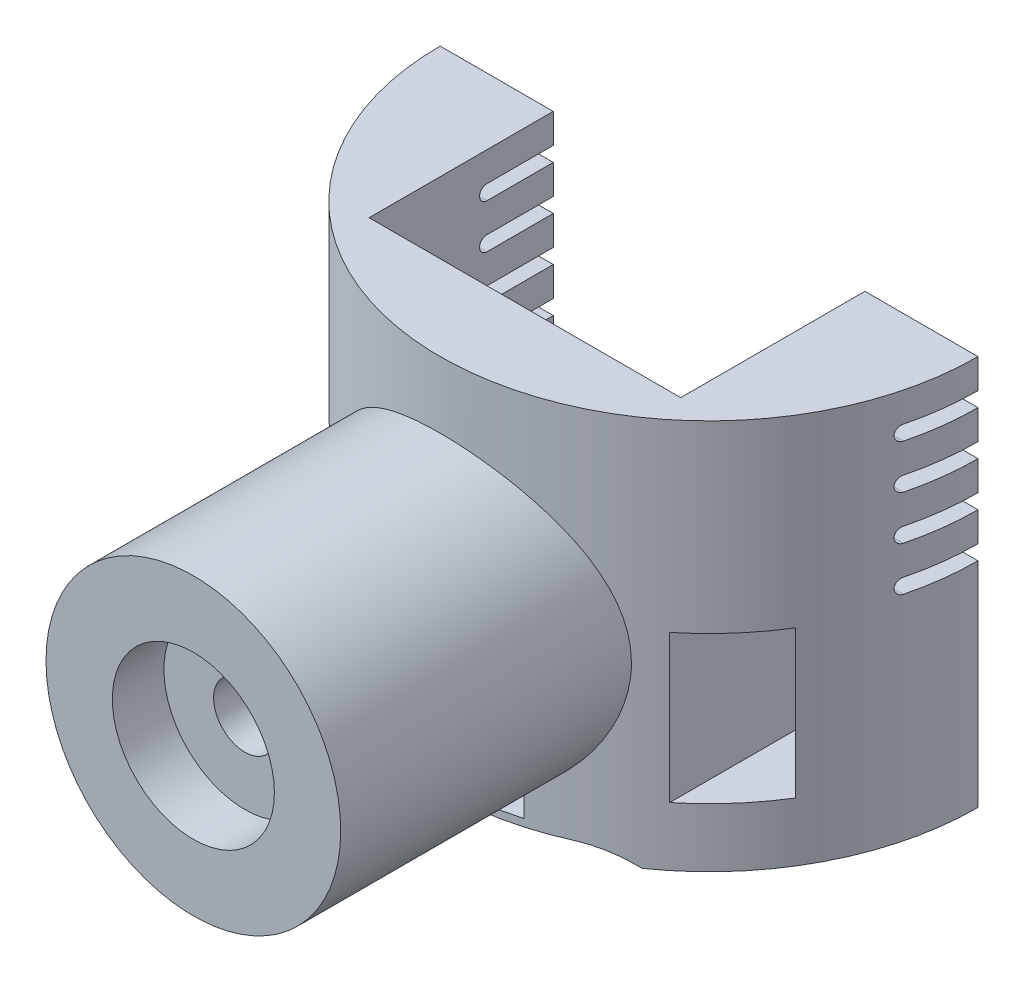
SolidWorks part; units mm, degrees
ref_plane "Front Plane" through (0, 0, 0) normal (0, 0, 1) x (1, 0, 0)
ref_plane "Top Plane" through (0, 0, 0) normal (0, 1, 0) x (1, 0, 0)
ref_plane "Right Plane" through (0, 0, 0) normal (1, 0, 0) x (0, 0, -1)
sketch "Sketch1" plane through (0, 0, 0) normal (0, 1, 0) x (1, 0, 0)
  circle A0 centre (0, 0) radius 36.5
  dimension "D1" = 73
extrude "Boss-Extrude1" add sketch "Sketch1" along normal blind 3
sketch "Sketch2" plane through (0, 3, 0) normal (0, 1, 0) x (1, 0, 0)
  line L0 (-11, 0) -> (-11, -34.803)
  line L1 (11, 0) -> (11, -34.803)
  arc A0 (11, -34.803) -> (-11, -34.803) centre (0, 0) ccw
  arc A1 (11, 0) -> (-11, 0) centre (0, 0) ccw
  dimension "D1" = 73
  dimension "D2" = 11
extrude "Boss-Extrude2" add sketch "Sketch2" along normal blind 7
sketch "Sketch3" plane through (0, 3, 0) normal (0, 1, 0) x (1, 0, 0)
  circle A0 centre (0, 0) radius 4.15
  dimension "D1" = 8.3
extrude "Cut-Extrude1" cut sketch "Sketch3" against normal up to next
sketch "Sketch4" plane through (0, 10, 0) normal (0, 1, 0) x (1, 0, 0)
  line L1 (-6.35, -3.6662) -> (-6.35, -35.9434)
  line L3 (6.35, -3.6662) -> (6.35, 3.6662)
  line L4 (6.35, 3.6662) -> (0, 7.3323)
  line L5 (0, 7.3323) -> (-6.35, 3.6662)
  line L6 (-6.35, 3.6662) -> (-6.35, -3.6662)
  line L8 (6.35, -3.6662) -> (6.35, -35.9434)
  line L10 (-3.175, -5.4993) -> (-0.7775, -6.8834) [skipped]
  line L11 (3.175, -5.4993) -> (6.35, -3.6662) [skipped]
  arc A0 (6.35, -35.9434) -> (-6.35, -35.9434) centre (0, 0) ccw
  arc A1 (6.35, 0) -> (-6.35, 0) centre (0, 0) ccw construction
  arc A2 (6.35, -35.9434) -> (-6.35, -35.9434) centre (0, 0) ccw
  arc M3 (-11, 0) -> (11, 0) centre (0, 0) cw
  line M4 (11, 0) -> (11, -34.803)
  arc M5 (11, -34.803) -> (-11, -34.803) centre (0, 0) ccw
  line M6 (-11, -34.803) -> (-11, 0)
  dimension "D1" = 73
  dimension "D2" = 6.35
extrude "Boss-Extrude3" add sketch "Sketch4" along normal blind 8 contours M6 M3 M4 M5 | L8 A0 L1 L6 L5 L4 L3 M4 M3 M6 region at (-6.8684, 10, 19.8048) region at (0, 10, -35.4796)
sketch "Sketch5" plane through (0, 18, 0) normal (0, 1, 0) x (1, 0, 0)
  line L5 (0, 0) -> (24, 21.15) construction
  circle A0 centre (0, 0) radius 36.5
  dimension "D1" = 73
extrude "Boss-Extrude4" add sketch "Sketch5" along normal blind 5
sketch "Sketch6" plane through (0, 23, 0) normal (0, 1, 0) x (1, 0, 0)
  line L1 (-21.15, -25) -> (21.15, -25)
  line L2 (-21.15, -25) -> (-21.15, 25)
  line L3 (-21.15, 25) -> (21.15, 25)
  line L4 (21.15, -25) -> (21.15, 25)
  line L5 (-21.15, -25) -> (21.15, 25) construction
  line L6 (-21.15, 25) -> (21.15, -25) construction
  circle A0 centre (0, 0) radius 36.5
  dimension "D1" = 73
  dimension "D2" = 42.3
  dimension "D3" = 50
extrude "Boss-Extrude5" add sketch "Sketch6" along normal blind 50
ref_plane "Plane1" through (0, 0, 38.6) normal (0, 0, -1) x (-1, 0, 0)
sketch "Sketch7" plane through (0, 0, 38.6) normal (0, 0, -1) x (-1, 0, 0)
  line L0 (-36.5, 0) -> (36.5, 0) construction
  line L1 (-14.8667, 2) -> (14.8667, 2)
  line L3 (-14.8667, 22) -> (14.8667, 22)
  line L6 (-5.6045, 15.7698) -> (5.6045, 8.2302) construction
  line L7 (0, 12) -> (5.6045, 15.7698) construction
  arc A0 (-14.8667, 22) -> (-14.8667, 2) centre (-14.8667, 12) ccw
  arc A1 (14.8667, 2) -> (14.8667, 22) centre (14.8667, 12) ccw
  point P0 (0, 12)
  dimension "D1" = 12
  dimension "D2" = 20
extrude "Cut-Extrude3" cut sketch "Sketch7" along normal blind 12
sketch "Sketch9" plane through (0, 0, 0) normal (0, 0, 1) x (1, 0, 0)
  line L1 (0, 0) -> (54.5049, 0)
  line L2 (0, 0) -> (0, 78.124)
  line L3 (0, 78.124) -> (54.5049, 78.124)
  line L4 (54.5049, 0) -> (54.5049, 78.124)
ref_plane "Plane3" through (0, 0, 70) normal (0, 0, 1) x (1, 0, 0)
sketch "Sketch11" plane through (0, 0, 70) normal (0, 0, 1) x (1, 0, 0)
  line L0 (38.5, 0) -> (-38.5, 0) construction
  circle A0 centre (0, 44) radius 20
  dimension "D1" = 40
  dimension "D2" = 44
extrude "Boss-Extrude7" add sketch "Sketch11" against normal up to next
revolve "Cut-Revolve1" cut sketch "Sketch9" angle 180 about L2
ref_plane "Plane2" through (0, 0, 70) normal (0, 0, 1) x (1, 0, 0)
sketch "Sketch12" plane through (0, 0, 70) normal (0, 0, 1) x (1, 0, 0)
  circle A0 centre (0, 44) radius 11
  dimension "D1" = 22
extrude "Cut-Extrude4" cut sketch "Sketch12" against normal blind 7
sketch "Sketch13" plane through (0, 0, 63) normal (0, 0, 1) x (1, 0, 0)
  circle A0 centre (0, 44) radius 4.25
  dimension "D1" = 8.5
extrude "Cut-Extrude5" cut sketch "Sketch13" against normal up to next
sketch "Sketch14" plane through (0, 0, 25) normal (0, 0, -1) x (-1, 0, 0)
  circle A0 centre (0, 44) radius 11
  dimension "D1" = 22
extrude "Cut-Extrude6" cut sketch "Sketch14" against normal blind 31
ref_plane "Plane4" through (0, 0, 5) normal (0, 0, 1) x (1, 0, 0)
sketch "Sketch16" plane through (0, 0, 5) normal (0, 0, 1) x (1, 0, 0)
  line L0 (36.5, 73) -> (-36.5, 73) construction
  line L1 (-31, 48) -> (-23, 48)
  line L2 (-31, 48) -> (-31, 28)
  line L3 (-31, 28) -> (-23, 28)
  line L4 (-23, 48) -> (-23, 28)
  line L5 (23, 48) -> (31, 48)
  line L6 (23, 48) -> (23, 28)
  line L7 (23, 28) -> (31, 28)
  line L8 (31, 48) -> (31, 28)
  line L9 (0, -38.5) -> (0, 38.5) construction
  dimension "D1" = 20
  dimension "D2" = 8
  dimension "D3" = 25
  dimension "D4" = 23
  dimension "D5" = 23
  dimension "D6" = 8
  dimension "D7" = 20
  dimension "D8" = 25
extrude "Cut-Extrude7" cut sketch "Sketch16" along normal up to next
sketch "Sketch17" plane through (0, 0, 5) normal (0, 0, 1) x (1, 0, 0)
  line L0 (-23, 48) -> (-23, 28) construction
  line L1 (-31, 48) -> (-23, 48) construction
  line L2 (23, 28) -> (23, 48) construction
  line L3 (23, 48) -> (23, 28) construction
  line L4 (23, 48) -> (31, 48) construction
  line L5 (-23, 28) -> (-23, 48) construction
  circle A0 centre (27, 42) radius 1.375
  circle A1 centre (27, 34) radius 1.375
  circle A2 centre (-27, 42) radius 1.375
  circle A3 centre (-27, 34) radius 1.375
  dimension "D4" = 2.75
  dimension "D5" = 2.75
  dimension "D6" = 2.75
  dimension "D7" = 2.75
  dimension "D1" = 4
  dimension "D2" = 6
  dimension "D3" = 8
  dimension "D8" = 4
  dimension "D9" = 8
  dimension "D10" = 4
  dimension "D11" = 6
  dimension "D12" = 4
extrude "Cut-Extrude8" cut sketch "Sketch17" against normal up to next
sketch "Sketch18" plane through (0, 0, 25) normal (0, 0, -1) x (-1, 0, 0)
  line L0 (21.15, 23) -> (-21.15, 23) construction
  line L1 (-10, 23) -> (10, 23)
  line L2 (-10, 23) -> (-10, 31.9)
  line L3 (-10, 31.9) -> (10, 31.9)
  line L4 (10, 23) -> (10, 31.9)
  line L5 (21.15, 73) -> (21.15, 23) construction
  point P8 (0, 31.9)
  dimension "D1" = 21.15
  dimension "D2" = 20
  dimension "D3" = 8.9
extrude "Cut-Extrude9" cut sketch "Sketch18" against normal blind 15
sketch "Sketch19" plane through (0, 0, 5) normal (0, 0, 1) x (1, 0, 0)
  line L1 (-23.94, 42) -> (-25.47, 44.65)
  line L2 (-25.47, 44.65) -> (-28.53, 44.65)
  line L3 (-28.53, 44.65) -> (-30.06, 42)
  line L4 (-30.06, 42) -> (-28.53, 39.35)
  line L5 (-28.53, 39.35) -> (-25.47, 39.35)
  line L6 (-25.47, 39.35) -> (-23.94, 42)
  line L7 (-23.94, 34) -> (-25.47, 36.65)
  line L8 (-25.47, 36.65) -> (-28.53, 36.65)
  line L9 (-28.53, 36.65) -> (-30.06, 34)
  line L10 (-30.06, 34) -> (-28.53, 31.35)
  line L11 (-28.53, 31.35) -> (-25.47, 31.35)
  line L12 (-25.47, 31.35) -> (-23.94, 34)
  line L13 (30.06, 42) -> (28.53, 44.65)
  line L14 (28.53, 44.65) -> (25.47, 44.65)
  line L15 (25.47, 44.65) -> (23.94, 42)
  line L16 (23.94, 42) -> (25.47, 39.35)
  line L17 (25.47, 39.35) -> (28.53, 39.35)
  line L18 (28.53, 39.35) -> (30.06, 42)
  line L19 (30.06, 34) -> (28.53, 36.65)
  line L20 (28.53, 36.65) -> (25.47, 36.65)
  line L21 (25.47, 36.65) -> (23.94, 34)
  line L22 (23.94, 34) -> (25.47, 31.35)
  line L23 (25.47, 31.35) -> (28.53, 31.35)
  line L24 (28.53, 31.35) -> (30.06, 34)
  circle A0 centre (-27, 42) radius 2.65 construction
  circle A1 centre (-27, 34) radius 2.65 construction
  circle A2 centre (27, 42) radius 2.65 construction
  circle A3 centre (27, 34) radius 2.65 construction
  dimension "D1" = 5.3
  dimension "D2" = 5.3
  dimension "D3" = 5.3
  dimension "D4" = 5.3
extrude "Cut-Extrude10" cut sketch "Sketch19" against normal blind 2.1
ref_plane "Plane5" through (36.5, 0, 0) normal (1, 0, 0) x (0, 0, -1)
sketch "Sketch20" plane through (36.5, 0, 0) normal (1, 0, 0) x (0, 0, -1)
  line L0 (0, 73) -> (-36.5, 73) construction
  line L1 (0, 69) -> (-10, 69)
  line L2 (0, 69) -> (0, 67)
  line L3 (0, 67) -> (-10, 67)
  line L4 (-10, 69) -> (-10, 67)
  line L5 (0, 63) -> (-10, 63)
  line L6 (0, 63) -> (0, 61)
  line L7 (0, 61) -> (-10, 61)
  line L8 (-10, 63) -> (-10, 61)
  line L9 (0, 40.15) -> (0, -40.15) construction
  line L10 (0, 57) -> (-10, 57)
  line L11 (0, 57) -> (0, 55)
  line L12 (0, 55) -> (-10, 55)
  line L13 (-10, 57) -> (-10, 55)
  line L14 (0, 51) -> (-10, 51)
  line L15 (0, 51) -> (0, 49)
  line L16 (0, 49) -> (-10, 49)
  line L17 (-10, 51) -> (-10, 49)
  dimension "D1" = 2
  dimension "D2" = 2
  dimension "D3" = 4
  dimension "D4" = 4
  dimension "D5" = 4
  dimension "D6" = 2
  dimension "D7" = 4
  dimension "D8" = 2
  dimension "D9" = 10
  dimension "D10" = 0
  dimension "D11" = 10
  dimension "D12" = 0
  dimension "D13" = 10
  dimension "D14" = 10
  dimension "D15" = 0
extrude "Cut-Extrude11" cut sketch "Sketch20" against normal through all
fillet "Fillet1" radius 1 16 edges at (-28.1267, 55, 10) (-28.1267, 61, 10) (-28.1267, 67, 10) (-28.1267, 69, 10) (-28.1267, 63, 10) (-28.1267, 57, 10) (-28.1267, 51, 10) (-28.1267, 49, 10) (28.1267, 51, 10) (28.1267, 49, 10) (28.1267, 55, 10) (28.1267, 57, 10) (28.1267, 63, 10) (28.1267, 61, 10) (28.1267, 69, 10) (28.1267, 67, 10)
sketch "Sketch21" plane through (0, 0, 0) normal (0, -1, 0) x (1, 0, 0)
  circle A0 centre (0, 0) radius 36.5
extrude "Cut-Extrude12" cut sketch "Sketch21" against normal blind 20
